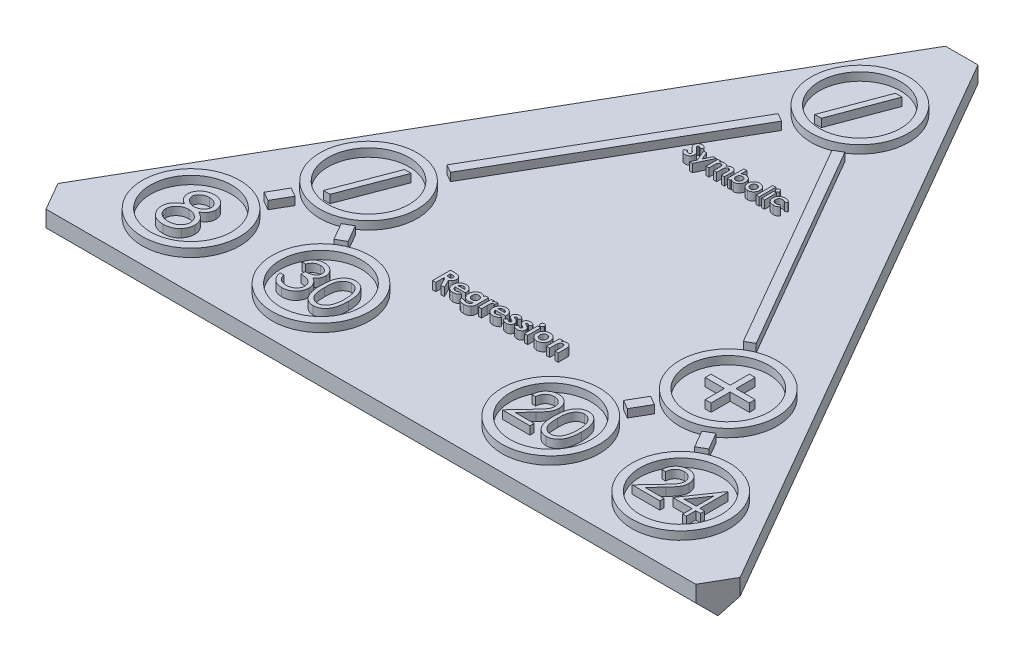
SolidWorks part; units mm, degrees
ref_plane "Front Plane" through (0, 0, 0) normal (0, 0, 1) x (1, 0, 0)
ref_plane "Top Plane" through (0, 0, 0) normal (0, 1, 0) x (1, 0, 0)
ref_plane "Right Plane" through (0, 0, 0) normal (1, 0, 0) x (0, 0, -1)
sketch "Sketch2" plane through (0, 0, 0) normal (0, 1, 0) x (1, 0, 0)
  line L0 (3.175, 75.1566) -> (-3.175, 75.1566)
  line L1 (-3.175, 75.1566) -> (-66.675, -34.8287)
  line L2 (-63.5, -40.3279) -> (63.5, -40.3279)
  line L3 (66.675, -34.8287) -> (3.175, 75.1566)
  line L4 (63.5, -40.3279) -> (66.675, -34.8287)
  line L5 (-66.675, -34.8287) -> (-63.5, -40.3279)
  circle A0 centre (0, 0) radius 40.3279 construction
  point P2 (0, 80.6558)
  point P3 (-69.85, -40.3279)
  point P4 (69.85, -40.3279)
  dimension "D1" = 139.7
extrude "Boss-Extrude1" add sketch "Sketch2" against normal blind 3.175
sketch "Sketch3" plane through (0, 0, 0) normal (0, 1, 0) x (1, 0, 0)
  line L0 (0, 55.2558) -> (0, 29.8558) construction
  line L1 (-15.4161, 29.8558) -> (15.4161, 29.8558) construction
  line L2 (0, 29.8558) -> (0, -16.2198) construction
  line L3 (-18.6015, -16.2198) -> (18.6015, -16.2198) construction
  line L5 (-47.853, -27.6279) -> (-35.153, -5.6309) construction
  line L6 (-35.153, -5.6309) -> (-22.453, -27.6279) construction
  line L7 (-22.453, -27.6279) -> (-47.853, -27.6279) construction
  line L8 (35.153, -5.6309) -> (22.453, -27.6279) construction
  line L9 (22.453, -27.6279) -> (47.853, -27.6279) construction
  line L10 (47.853, -27.6279) -> (35.153, -5.6309) construction
  line L11 (-63.5, -40.3279) -> (63.5, -40.3279) construction
  line L13 (-3.175, 75.1566) -> (-66.675, -34.8287) construction
  line L14 (66.675, -34.8287) -> (3.175, 75.1566) construction
  line L15 (0, 55.2558) -> (0, 50.9403) construction
  line L16 (-35.153, -5.6309) -> (-35.153, -9.9464) construction
  line L17 (-47.853, -27.6279) -> (-47.853, -32.7771) construction
  line L18 (-22.453, -27.6279) -> (-22.453, -31.9435) construction
  line L19 (35.153, -5.6309) -> (35.153, -11.6942) construction
  line L20 (22.453, -27.6279) -> (22.453, -31.3004) construction
  line L21 (47.853, -27.6279) -> (47.853, -31.3004) construction
  line L22 (-6.6618, 50.9403) -> (6.6618, 50.9403) construction
  line L23 (-41.8148, -9.9464) -> (-28.4911, -9.9464) construction
  line L24 (-53.8936, -32.7771) -> (-41.8123, -32.7771) construction
  line L25 (-29.1148, -31.9435) -> (-15.7911, -31.9435) construction
  line L26 (30.0305, -11.6942) -> (40.2754, -11.6942) construction
  line L27 (15.4161, -31.3004) -> (29.4898, -31.3004) construction
  line L28 (40.8161, -31.3004) -> (54.8898, -31.3004) construction
  circle A0 centre (0, 55.2558) radius 9.525 construction
  circle A1 centre (-47.853, -27.6279) radius 9.525 construction
  circle A2 centre (-22.453, -27.6279) radius 9.525 construction
  circle A3 centre (22.453, -27.6279) radius 9.525 construction
  circle A4 centre (47.853, -27.6279) radius 9.525 construction
  circle A5 centre (-35.153, -5.6309) radius 9.525 construction
  circle A6 centre (35.153, -5.6309) radius 9.525 construction
  circle A7 centre (0, 55.2558) radius 7.9375 construction
  circle A8 centre (-35.153, -5.6309) radius 7.9375 construction
  circle A9 centre (35.153, -5.6309) radius 7.9375 construction
  circle A10 centre (-47.853, -27.6279) radius 7.9375 construction
  circle A11 centre (-22.453, -27.6279) radius 7.9375 construction
  circle A12 centre (22.453, -27.6279) radius 7.9375 construction
  circle A13 centre (47.853, -27.6279) radius 7.9375 construction
  text T0 "/" font "Century Gothic" height 9.525
  text T1 "/" font "Century Gothic" height 9.525
  text T2 "8" font "Century Gothic" height 9.525
  text T3 "30" font "Century Gothic" height 7.9375
  text T4 "+" font "Century Gothic" height 12.7
  text T5 "20\r\n" font "Century Gothic" height 7.9375
  text T6 "24\r\n" font "Century Gothic" height 7.9375
  text T7 "Symbolic" font "Century Gothic" height 3.175
  text T8 "<b>Regression</b>"
  point P36 (0, 50.9403)
  point P41 (-35.153, -9.9464)
  point P43 (-47.853, -32.7771)
  point P46 (-22.453, -31.9435)
  point P51 (35.153, -11.6942)
  point P54 (22.453, -31.3004)
  point P57 (47.853, -31.3004)
  point P62 (0, 29.8558)
  point P63 (0, 29.8558)
  point P64 (0, 29.8558)
  point P70 (0, -16.2198)
  dimension "D1" = 19.05
  dimension "D2" = 1.5875
  dimension "D3" = 25.4
  dimension "D4" = 12.7
  dimension "D5" = 12.7
  dimension "D6" = 12.7
  dimension "D7" = 12.7
  dimension "D8" = 12.7
  dimension "D9" = 12.7
  dimension "D10" = 25.4
sketch "Sketch4" plane through (0, -3.175, 0) normal (0, -1, 0) x (1, 0, 0)
  line L6 (-66.675, 34.8287) -> (-3.175, -75.1566)
  line L7 (-3.175, -75.1566) -> (3.175, -75.1566)
  line L8 (3.175, -75.1566) -> (66.675, 34.8287)
  line L9 (66.675, 34.8287) -> (63.5, 40.3279)
  line L10 (63.5, 40.3279) -> (-63.5, 40.3279)
  line L11 (-63.5, 40.3279) -> (-66.675, 34.8287)
  line L12 (-66.675, 34.8287) -> (-3.175, -75.1566)
  line L13 (-3.175, -75.1566) -> (3.175, -75.1566)
  line L14 (3.175, -75.1566) -> (66.675, 34.8287)
  line L15 (66.675, 34.8287) -> (63.5, 40.3279)
  line L16 (63.5, 40.3279) -> (-63.5, 40.3279)
  line L17 (-63.5, 40.3279) -> (-66.675, 34.8287)
  dimension "D1" = 0
extrude "Boss-Extrude3" add sketch "Sketch4" along normal blind 12.7
chamfer "Chamfer1" distance 12.7 angle 45 3 edges at (0, -15.875, 40.3279) (34.925, -15.875, -20.164) (-34.925, -15.875, -20.164)
extrude "Boss-Extrude4" add sketch "Sketch3" along normal blind 1.5875
sketch "Sketch9" plane through (0, 0, 0) normal (0, 1, 0) x (1, 0, 0)
  line L0 (-35.153, -5.6309) -> (0, 55.2558) construction
  line L1 (0, 55.2558) -> (35.153, -5.6309) construction
  line L5 (-47.853, -27.6279) -> (-35.153, -5.6309) construction
  line L6 (-35.153, -5.6309) -> (-22.453, -27.6279) construction
  line L7 (-22.453, -27.6279) -> (-47.853, -27.6279) construction
  line L8 (35.153, -5.6309) -> (22.453, -27.6279) construction
  line L9 (22.453, -27.6279) -> (47.853, -27.6279) construction
  line L10 (47.853, -27.6279) -> (35.153, -5.6309) construction
  line L12 (-4.9337, 44.8646) -> (-6.5323, 45.7875)
  line L13 (-4.9337, 44.8646) -> (-28.6207, 3.8375)
  line L15 (0, 55.2558) -> (0, 50.9403) construction
  line L16 (-35.153, -5.6309) -> (-35.153, -9.9464) construction
  line L17 (-47.853, -27.6279) -> (-47.853, -32.7771) construction
  line L18 (-22.453, -27.6279) -> (-22.453, -31.9435) construction
  line L19 (35.153, -5.6309) -> (35.153, -11.6942) construction
  line L20 (22.453, -27.6279) -> (22.453, -31.3004) construction
  line L21 (47.853, -27.6279) -> (47.853, -31.3004) construction
  line L22 (-6.6618, 50.9403) -> (6.6618, 50.9403) construction
  line L23 (-41.8148, -9.9464) -> (-28.4911, -9.9464) construction
  line L24 (-53.8936, -32.7771) -> (-41.8123, -32.7771) construction
  line L25 (-29.1148, -31.9435) -> (-15.7911, -31.9435) construction
  line L26 (30.0305, -11.6942) -> (40.2754, -11.6942) construction
  line L27 (15.4161, -31.3004) -> (29.4898, -31.3004) construction
  line L28 (40.8161, -31.3004) -> (54.8898, -31.3004) construction
  line L32 (-6.5323, 45.7875) -> (-30.2193, 4.7604)
  line L33 (-28.6207, 3.8375) -> (-30.2193, 4.7604)
  line L34 (-43.4571, -17.7372) -> (-41.701, -18.751)
  line L35 (-43.4571, -17.7372) -> (-41.5207, -14.3832)
  line L36 (-41.701, -18.751) -> (-39.7646, -15.397)
  line L37 (-41.5207, -14.3832) -> (-39.7646, -15.397)
  line L38 (-43.4571, -17.7372) -> (-39.7646, -15.397) construction
  line L39 (-41.701, -18.751) -> (-41.5207, -14.3832) construction
  line L40 (-28.676, -18.877) -> (-26.92, -17.8631)
  line L41 (-28.676, -18.877) -> (-30.6125, -15.523)
  line L42 (-26.92, -17.8631) -> (-28.8564, -14.5091)
  line L43 (-30.6125, -15.523) -> (-28.8564, -14.5091)
  line L44 (-28.676, -18.877) -> (-28.8564, -14.5091) construction
  line L45 (-26.92, -17.8631) -> (-30.6125, -15.523) construction
  line L50 (-4.9337, 44.8646) -> (-30.2193, 4.7604) construction
  line L51 (-6.5323, 45.7875) -> (-28.6207, 3.8375) construction
  line L56 (0, -1.7463) -> (0, 1.7463) construction
  line L57 (28.676, -18.877) -> (26.92, -17.8631)
  line L58 (26.92, -17.8631) -> (28.8564, -14.5091)
  line L59 (30.6125, -15.523) -> (28.8564, -14.5091)
  line L60 (28.676, -18.877) -> (30.6125, -15.523)
  line L61 (43.4571, -17.7372) -> (41.701, -18.751)
  line L62 (43.4571, -17.7372) -> (41.5207, -14.3832)
  line L63 (41.5207, -14.3832) -> (39.7646, -15.397)
  line L64 (41.701, -18.751) -> (39.7646, -15.397)
  line L65 (28.6207, 3.8375) -> (30.2193, 4.7604)
  line L66 (6.5323, 45.7875) -> (30.2193, 4.7604)
  line L67 (4.9337, 44.8646) -> (6.5323, 45.7875)
  line L68 (4.9337, 44.8646) -> (28.6207, 3.8375)
  circle A0 centre (0, 55.2558) radius 9.525
  circle A1 centre (-47.853, -27.6279) radius 9.525
  circle A2 centre (-22.453, -27.6279) radius 9.525
  circle A3 centre (22.453, -27.6279) radius 9.525
  circle A4 centre (47.853, -27.6279) radius 9.525
  circle A5 centre (-35.153, -5.6309) radius 9.525
  circle A6 centre (35.153, -5.6309) radius 9.525
  circle A7 centre (0, 55.2558) radius 7.9375
  circle A8 centre (-35.153, -5.6309) radius 7.9375
  circle A9 centre (35.153, -5.6309) radius 7.9375
  circle A10 centre (-47.853, -27.6279) radius 7.9375
  circle A11 centre (-22.453, -27.6279) radius 7.9375
  circle A12 centre (22.453, -27.6279) radius 7.9375
  circle A13 centre (47.853, -27.6279) radius 7.9375
  point P22 (-17.5765, 24.8125)
  point P23 (-41.6108, -16.5671)
  point P36 (0, 50.9403)
  point P41 (-35.153, -9.9464)
  point P43 (-47.853, -32.7771)
  point P46 (-22.453, -31.9435)
  point P50 (-28.7662, -16.693)
  point P51 (35.153, -11.6942)
  point P54 (22.453, -31.3004)
  point P57 (47.853, -31.3004)
  dimension "D1" = 19.05
  dimension "D2" = 1.5875
  dimension "D3" = 25.4
extrude "Boss-Extrude5" add sketch "Sketch9" along normal blind 1.5875
sketch "Sketch10" plane through (0, -15.875, 0) normal (0, -1, 0) x (1, 0, 0)
  line L0 (0, 27.6279) -> (0, 7.3079) construction
  line L1 (47.853, 27.6279) -> (-47.853, 27.6279) construction
  dimension "D1" = 20.32
ref_plane "Plane1" through (0, -21.7515, 21.7515) normal (0, -0.7071, 0.7071) x (-1, 0, 0)
sketch "Sketch11" plane through (0, -21.7515, 21.7515) normal (0, -0.7071, 0.7071) x (-1, 0, 0)
  circle A0 centre (0, 6.0578) radius 3.9688
  circle A1 centre (0, 6.0578) radius 2.3813
  dimension "D1" = 7.9375
  dimension "D2" = 4.7625
ref_plane "Plane2" through (0, 14.1696, -14.1696) normal (0, -0.7071, 0.7071) x (-1, 0, 0)
sketch "Sketch12" plane through (0, 14.1696, -14.1696) normal (0, -0.7071, 0.7071) x (-1, 0, 0)
  circle A0 centre (0, 6.0578) radius 6.35
  circle A1 centre (0, 6.0578) radius 2.3813
  circle A2 centre (0, 6.0578) radius 2.3813 construction
  circle A3 centre (0, 6.0578) radius 3.9688
  circle A4 centre (0, 6.0578) radius 3.9688 construction
  dimension "D3" = 12.7
  dimension "D1" = 0
  dimension "D2" = 0
sketch "Sketch13" plane through (0, 0, 0) normal (0, 1, 0) x (1, 0, 0)
  circle A0 centre (0, 21.2671) radius 3 construction
  circle A1 centre (0, 21.2671) radius 3
